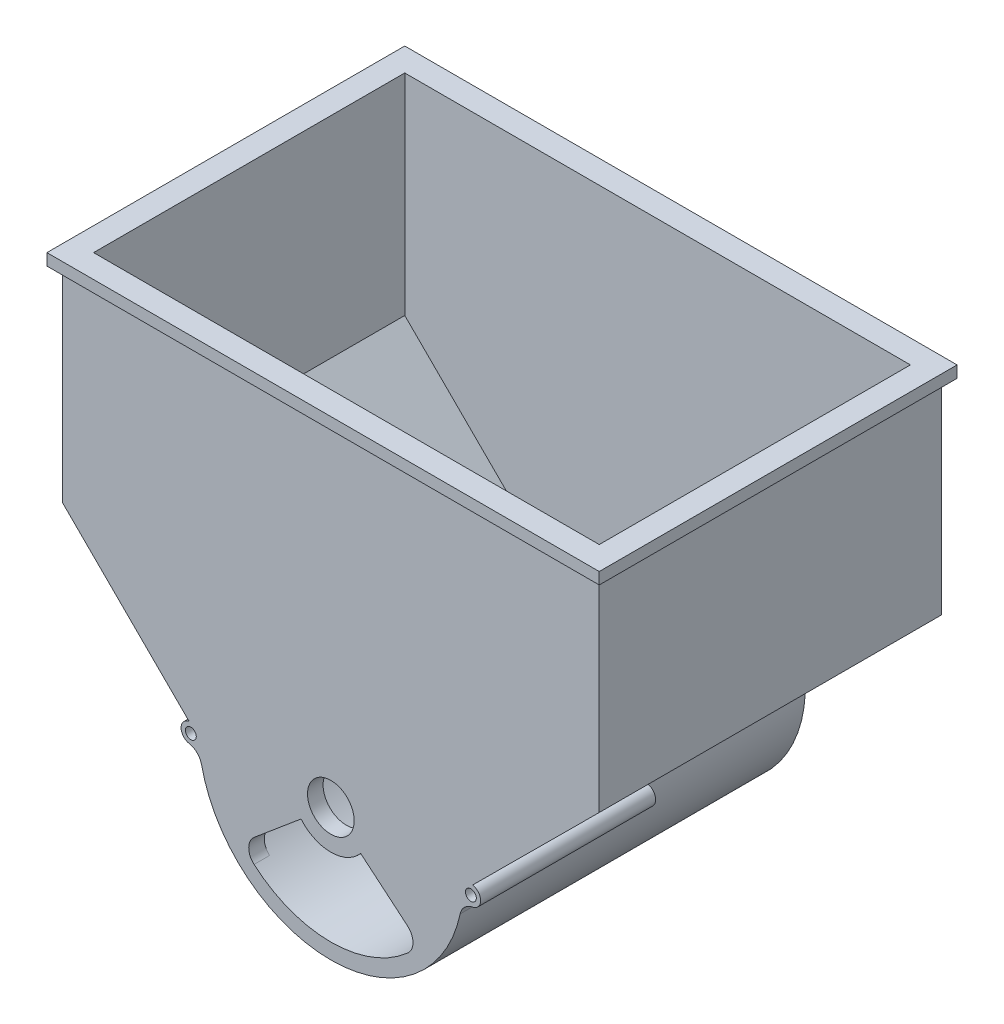
SolidWorks part; units mm, degrees
ref_plane "前基準面" through (0, 0, 0) normal (0, 0, 1) x (1, 0, 0)
ref_plane "上基準面" through (0, 0, 0) normal (0, 1, 0) x (1, 0, 0)
ref_plane "右基準面" through (0, 0, 0) normal (1, 0, 0) x (0, 0, -1)
sketch "草圖1" plane through (0, 0, 0) normal (0, 0, 1) x (1, 0, 0)
  line L0 (65, 50) -> (65, -35) construction
  line L2 (0, 0) -> (0, 50)
  line L3 (0, 50) -> (130, 50)
  line L4 (130, 0) -> (130, 50)
  line L5 (0, 0) -> (35.0004, -34.8465)
  line L6 (130, 0) -> (94.9996, -34.8465)
  line L7 (-4, -1.662) -> (-4, 54)
  line L8 (-4, 54) -> (134, 54)
  line L9 (134, -1.662) -> (134, 54)
  line L10 (134, -1.662) -> (98.965, -36.543)
  line L11 (-4, -1.662) -> (31.035, -36.543)
  arc A0 (35.0004, -34.8465) -> (94.9996, -34.8465) centre (65, -35) ccw
  arc A1 (31.035, -36.543) -> (98.965, -36.543) centre (65, -35) ccw
  dimension "D4" = 60
  dimension "D1" = 130
  dimension "D2" = 50
  dimension "D3" = 85
  dimension "D5" = 4
  dimension "D6" = 50
extrude "填料-伸長1" add sketch "草圖1" along normal blind 80
sketch "草圖2" plane through (0, 0, 80) normal (0, 0, 1) x (1, 0, 0)
  line L5 (-4, 54) -> (-4, -1.662)
  line L6 (134, 54) -> (-4, 54)
  line L7 (134, -1.662) -> (134, 54)
  line L8 (98.965, -36.543) -> (134, -1.662)
  line L9 (-4, -1.662) -> (31.035, -36.543)
  line L10 (-4, 54) -> (-4, -1.662)
  line L11 (134, 54) -> (-4, 54)
  line L12 (134, -1.662) -> (134, 54)
  line L13 (98.965, -36.543) -> (134, -1.662)
  line L14 (-4, -1.662) -> (31.035, -36.543)
  line L15 (0, 50) -> (0, 0)
  line L16 (130, 50) -> (0, 50)
  line L17 (130, 0) -> (130, 50)
  line L18 (94.9996, -34.8465) -> (130, 0)
  line L19 (0, 0) -> (35.0004, -34.8465)
  arc A1 (31.035, -36.543) -> (98.965, -36.543) centre (65, -35) ccw
  arc A2 (31.035, -36.543) -> (98.965, -36.543) centre (65, -35) ccw
  arc A3 (35.0004, -34.8465) -> (94.9996, -34.8465) centre (65, -35) ccw
  arc A4 (35.0004, -34.8465) -> (94.9996, -34.8465) centre (65, -35) ccw
  line M13 (-4, -1.662) -> (31.035, -36.543)
  arc M14 (31.035, -36.543) -> (98.965, -36.543) centre (65, -35) ccw
  line M15 (98.965, -36.543) -> (134, -1.662)
  line M16 (134, -1.662) -> (134, 54)
  line M17 (134, 54) -> (-4, 54)
  line M18 (-4, 54) -> (-4, -1.662)
  arc M19 (94.9996, -34.8465) -> (35.0004, -34.8465) centre (65, -35) cw
  line M20 (35.0004, -34.8465) -> (0, 0)
  line M21 (0, 0) -> (0, 50)
  line M22 (0, 50) -> (130, 50)
  line M23 (130, 50) -> (130, 0)
  line M24 (130, 0) -> (94.9996, -34.8465)
  dimension "D1" = 0
  dimension "D2" = 0
extrude "填料-伸長2" add sketch "草圖2" along normal blind 4 contours M18 M13 M14 M15 M16 M17 M24 M19 M20 M21 M22 M23 | M19 M24 M23 M22 M21 M20 region at (65, 52.1514, 80) region at (65, 3.9261, 80)
sketch "草圖3" plane through (0, 0, 0) normal (0, 0, -1) x (-1, 0, 0)
  line L5 (4, -1.662) -> (4, 54)
  line L6 (-31.035, -36.543) -> (4, -1.662)
  line L7 (-134, -1.662) -> (-98.965, -36.543)
  line L8 (-134, 54) -> (-134, -1.662)
  line L9 (4, 54) -> (-134, 54)
  line L10 (4, -1.662) -> (4, 54)
  line L11 (-31.035, -36.543) -> (4, -1.662)
  line L12 (-134, -1.662) -> (-98.965, -36.543)
  line L13 (-134, 54) -> (-134, -1.662)
  line L14 (4, 54) -> (-134, 54)
  arc A0 (-94.9996, -34.8465) -> (-35.0004, -34.8465) centre (-65, -35) ccw construction
  arc A1 (-98.965, -36.543) -> (-31.035, -36.543) centre (-65, -35) ccw
  arc A2 (-98.965, -36.543) -> (-31.035, -36.543) centre (-65, -35) ccw
  arc A3 (-94.9996, -34.8465) -> (-35.0004, -34.8465) centre (-65, -35) ccw
  line M7 (-31.035, -36.543) -> (4, -1.662)
  line M8 (4, -1.662) -> (4, 54)
  line M9 (4, 54) -> (-134, 54)
  line M10 (-134, 54) -> (-134, -1.662)
  line M11 (-134, -1.662) -> (-98.965, -36.543)
  arc M12 (-98.965, -36.543) -> (-31.035, -36.543) centre (-65, -35) ccw
  line M13 (0, 0) -> (-35.0004, -34.8465)
  arc M14 (-35.0004, -34.8465) -> (-94.9996, -34.8465) centre (-65, -35) cw
  line M15 (-94.9996, -34.8465) -> (-130, 0)
  line M16 (-130, 0) -> (-130, 50)
  line M17 (-130, 50) -> (0, 50)
  line M18 (0, 50) -> (0, 0)
  dimension "D1" = 0
extrude "填料-伸長3" add sketch "草圖3" along normal blind 4 contours M13 M18 M17 M16 M15 M14 | M12 M7 M8 M9 M10 M11 M18 M13 M14 M15 M16 M17 region at (14.8218, -17.7925, 0) region at (65, 3.9261, 0)
sketch "草圖4" plane through (0, 54, 0) normal (0, 1, 0) x (1, 0, 0)
  line L0 (-4, -84) -> (-4, 4) construction
  line L1 (-4, 4) -> (134, 4)
  line L2 (-4, 4) -> (-4, -84)
  line L3 (-4, -84) -> (134, -84)
  line L4 (134, 4) -> (134, -84)
  line L5 (-4, 4) -> (134, 4) construction
  line L6 (0, 0) -> (130, 0)
  line L7 (130, 0) -> (130, -80)
  line L8 (0, -80) -> (130, -80)
  line L9 (0, 0) -> (0, -80)
  dimension "D1" = 4
extrude "除料-伸長1" cut sketch "草圖4" against normal blind 4 contours L6 L9 L8 L7 region at (65, 54, 40)
sketch "草圖5" plane through (0, 0, 84) normal (0, 0, 1) x (1, 0, 0)
  line L0 (65, 54) -> (65, -69) construction
  line L1 (134, 54) -> (-4, 54) construction
  arc A0 (31.035, -36.543) -> (98.965, -36.543) centre (65, -35) ccw construction
  circle A1 centre (65, -35) radius 6
  dimension "D1" = 12
extrude "除料-伸長2" cut sketch "草圖5" against normal up to surface (88 mm away) up to face at (65, -0.1445, -4)
sketch "草圖6" plane through (0, 0, 84) normal (0, 0, 1) x (1, 0, 0)
  line L0 (65, -35) -> (42.0187, -54.2836)
  line L1 (65, -35) -> (87.9813, -54.2836)
  line L2 (65, 54) -> (65, -69) construction
  line L3 (134, 54) -> (-4, 54) construction
  arc A0 (42.0187, -54.2836) -> (87.9813, -54.2836) centre (65, -35) ccw
  arc A1 (31.035, -36.543) -> (98.965, -36.543) centre (65, -35) ccw construction
  arc A2 (57.3396, -41.4279) -> (72.6604, -41.4279) centre (65, -35) ccw
  dimension "D1" = 4
  dimension "D2" = 20
  dimension "D3" = 50
  dimension "D4" = 50
extrude "除料-伸長3" cut sketch "草圖6" against normal up to surface (4 mm away) contours L2 A2 L0 A0 | A2 L2 A0 L1 region at (56.1311, -54.0195, 84) region at (73.8689, -54.0195, 84) up to face at (71, -35, 80)
sketch "草圖7" plane through (0, 0, -4) normal (0, 0, -1) x (-1, 0, 0)
  line L0 (-65, 54) -> (-65, -69) construction
  line L1 (4, 54) -> (-134, 54) construction
  circle A0 centre (-65, -43) radius 21
  circle A1 centre (-65, -35) radius 6 construction
  arc A2 (-98.965, -36.543) -> (-31.035, -36.543) centre (-65, -35) ccw construction
  dimension "D1" = 42
  dimension "D2" = 8
extrude "填料-伸長4" add sketch "草圖7" along normal blind 1
sketch "草圖9" plane through (0, 0, -5) normal (0, 0, -1) x (-1, 0, 0)
  line L0 (-65, -22) -> (-65, -64) construction
  line L1 (-86, -43) -> (-44, -43) construction
  circle A0 centre (-65, -35) radius 4.6
  circle A1 centre (-65, -43) radius 21
  circle A2 centre (-65, -43) radius 21
  circle A3 centre (-82.5, -43) radius 1.35
  circle A4 centre (-47.5, -43) radius 1.35
  dimension "D2" = 9.2
  dimension "D3" = 2.7
  dimension "D4" = 17.5
  dimension "D5" = 8
  dimension "D1" = 0
extrude "除料-伸長5" cut sketch "草圖9" against normal up to next contours A0 | A3 | A4 region at (65, -35, -5) region at (82.5, -43, -5) region at (47.5, -43, -5)
ref_plane "平面1" through (65, 0, 0) normal (1, 0, 0) x (0, 0, -1)
sketch "草圖10" plane through (65, 0, 0) normal (1, 0, 0) x (0, 0, -1)
  line L0 (-84, -69) -> (-84, 0) construction
  line L1 (-84, 28.7653) -> (-59, 1)
  line L3 (-84, 1) -> (-84, 28.7653)
  line L4 (-83, 26.1602) -> (-60.3456, 1)
  line L5 (-60.3456, 1) -> (-83, 1)
  line L6 (-83, 1) -> (-83, 26.1602)
  line L7 (-83, 1) -> (-84, 1)
  line L8 (-60.3456, 1) -> (-59, 1)
  line L9 (-84, 28.7653) -> (-58.0996, 0) construction
  line L10 (-58.0996, 0) -> (-84, 0) construction
  line L11 (-84, 1) -> (-84, 71.0976) construction
  line L12 (-84, 0) -> (-84, 28.7653) construction
  line L14 (-84, -1.662) -> (-84, 54) construction
  dimension "D1" = 1
  dimension "D2" = 42
  dimension "D3" = 70
  dimension "D4" = 25
extrude "填料-伸長5" add sketch "草圖10" along normal up to surface and the other way up to surface contours L4 L8 L1 L3 L7 L6 region at (65, 14.6327, 71.7777) up to face at (130, 27, 40) other way up to face at (0, 27, 40)
sketch "草圖11" plane through (0, 0, 84) normal (0, 0, 1) x (1, 0, 0)
  line L0 (-4, -1.662) -> (31.035, -36.543)
  line L1 (31.035, -36.543) -> (-4, -36.543)
  line L2 (-4, -36.543) -> (-4, -1.662)
  line L3 (134, -1.662) -> (98.965, -36.543)
  line L4 (98.965, -36.543) -> (134, -36.543)
  line L5 (134, -36.543) -> (134, -1.662)
extrude "除料-伸長6" [suppressed] cut sketch "草圖11" against normal up to surface (88 mm away) up to face at (44, -43, -4)
sketch "草圖12" plane through (0, 54, 0) normal (0, 1, 0) x (1, 0, 0)
  line L0 (-4, -84) -> (-4, 4) construction
  line L1 (-6, 6) -> (136, 6)
  line L2 (-6, 6) -> (-6, -86)
  line L3 (-6, -86) -> (136, -86)
  line L4 (136, 6) -> (136, -86)
  line L5 (-4, 4) -> (134, 4) construction
  line L6 (134, -84) -> (134, 4) construction
  line L7 (134, -84) -> (-4, -84) construction
  line L9 (-4, 4) -> (134, 4)
  line L10 (-4, 4) -> (-4, -84)
  line L11 (-4, -84) -> (134, -84)
  line L12 (134, 4) -> (134, -84)
  dimension "D1" = 2
  dimension "D2" = 2
  dimension "D3" = 2
  dimension "D4" = 2
extrude "填料-伸長6" add sketch "草圖12" against normal blind 3
chamfer "導角1" distance 1 angle 45 1 edges at (44, -43, -4)
sketch "草圖13" plane through (0, 0, 84) normal (0, 0, 1) x (1, 0, 0)
  line L0 (31.035, -36.543) -> (98.965, -36.543) construction
  line L1 (29, -36.543) -> (101, -36.543) construction
  line L2 (65, -69) -> (65, 51) construction
  line L3 (-4, 51) -> (134, 51) construction
  arc A0 (29.0868, -34.0445) -> (29.0272, -35.1432) centre (65, -36.543) ccw
  circle A2 centre (29, -36.543) radius 2.5
  circle A3 centre (29, -36.543) radius 1.4
  arc A4 (29.0272, -37.9427) -> (101, -36.543) centre (65, -36.543) ccw
  arc A5 (31.035, -36.543) -> (98.965, -36.543) centre (65, -35) ccw construction
  circle A6 centre (101, -36.543) radius 1.4
  circle A7 centre (101, -36.543) radius 2.5
  line M9 (-4, -1.662) -> (31.035, -36.543)
  arc M10 (31.035, -36.543) -> (98.965, -36.543) centre (65, -35) ccw
  line M11 (98.965, -36.543) -> (134, -1.662)
  dimension "D1" = 72
  dimension "D2" = 2.8
  dimension "D3" = 5
extrude "填料-伸長7" add sketch "草圖13" against normal blind 45 contours A3 A4 A2 A0 M10 M9 | A4 A3 A0 A2 M9 | A2 A0 M10 M9 | A0 A2 M9 | A7 A6 M11 M10 | A7 M10 M11 region at (30.466, -35.4427, 84) region at (28.8982, -34.2261, 84) region at (30.137, -37.5815, 84) region at (28.9836, -34.8543, 84) region at (98.9961, -37.2095, 84) region at (99.6002, -35.3913, 84)
fillet "圓角1" radius 4 2 edges at (42.0187, -54.2836, 82) (87.9813, -54.2836, 82)
fillet "圓角2" radius 4 2 edges at (31.121, -37.8663, 61.5) (98.879, -37.8663, 61.5)
